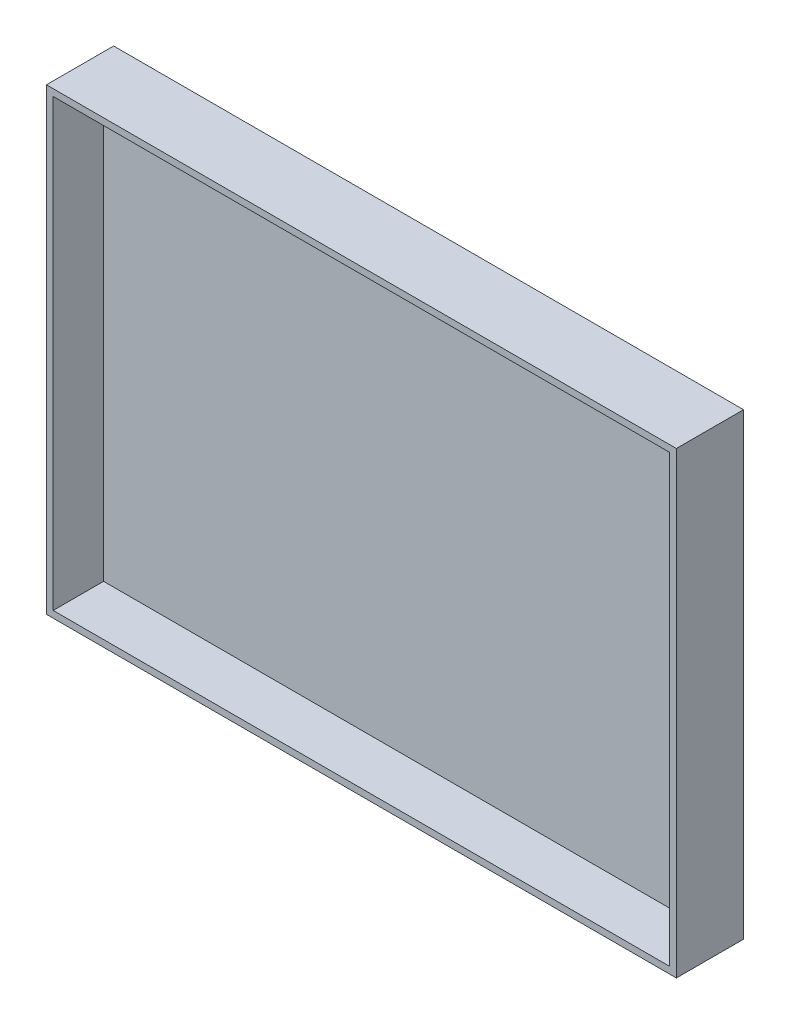
SolidWorks part; units mm, degrees
ref_plane "Plan de face" through (0, 0, 0) normal (0, 0, 1) x (1, 0, 0)
ref_plane "Plan de dessus" through (0, 0, 0) normal (0, 1, 0) x (1, 0, 0)
ref_plane "Plan de droite" through (0, 0, 0) normal (1, 0, 0) x (0, 0, -1)
sketch "Esquisse1" plane through (0, 0, 0) normal (0, 0, 1) x (1, 0, 0)
  line L1 (-18.35, 13.25) -> (18.35, 13.25)
  line L2 (-18.35, 13.25) -> (-18.35, -13.25)
  line L3 (-18.35, -13.25) -> (18.35, -13.25)
  line L4 (18.35, 13.25) -> (18.35, -13.25)
  line L5 (-18.35, 13.25) -> (18.35, -13.25) construction
  line L6 (-18.35, -13.25) -> (18.35, 13.25) construction
  point P0 (0, 0)
  dimension "D1" = 36.7
  dimension "D2" = 26.5
extrude "Boss.-Extru.2" add sketch "Esquisse1" along normal blind 1
extrude "Extru.-Mince1" add sketch "Esquisse1<2>" along normal blind 4 thin thin type one direction wall 0.4
sketch "Esquisse1<2>" plane through (0, 0, 0) normal (0, 0, 1) x (1, 0, 0) same geometry as "Esquisse1"
